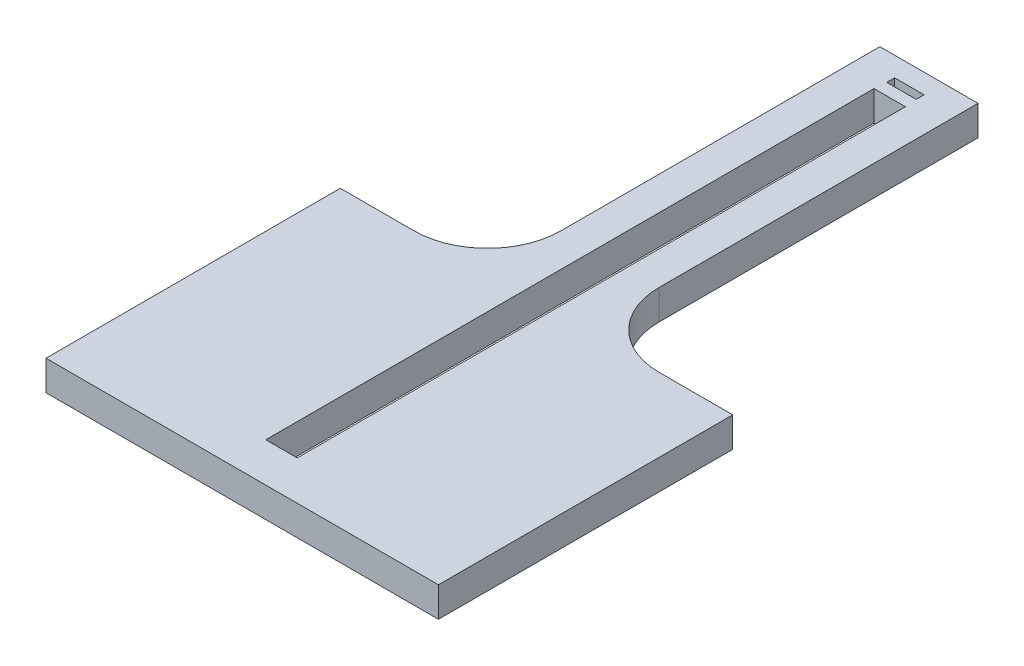
SolidWorks part; units mm, degrees
ref_plane "Front Plane" through (0, 0, 0) normal (0, 0, 1) x (1, 0, 0)
ref_plane "Top Plane" through (0, 0, 0) normal (0, 1, 0) x (1, 0, 0)
ref_plane "Right Plane" through (0, 0, 0) normal (1, 0, 0) x (0, 0, -1)
sketch "Sketch1" plane through (0, 0, 0) normal (0, 1, 0) x (1, 0, 0)
  line L1 (0, 0) -> (40, 0)
  line L2 (0, 0) -> (0, 70)
  line L3 (0, 70) -> (40, 70)
  line L4 (40, 0) -> (40, 70)
  dimension "D1" = 40
  dimension "D2" = 70
extrude "Boss-Extrude1" add sketch "Sketch1" along normal blind 3.05 contours L2 | L1 L4 L3 L2 | L4 region at (20, 0, -35)
sketch "Sketch4" plane through (0, 3.05, 0) normal (0, 1, 0) x (1, 0, 0)
  line L0 (20, 70) -> (20, 68)
  line L1 (0, 70) -> (40, 70) construction
  line L3 (21.5, 68) -> (18.5, 68)
  line L4 (18.5, 68) -> (18.5, 67.2)
  line L5 (18.5, 67.2) -> (21.5, 67.2)
  line L6 (21.5, 67.2) -> (21.5, 68)
  line L7 (20, 67.2) -> (20, 66)
  line L9 (21.6, 66) -> (18.4, 66)
  line L10 (18.4, 66) -> (18.4, 4)
  line L11 (18.4, 4) -> (21.6, 4)
  line L12 (21.6, 4) -> (21.6, 66)
  point P10 (20, 68)
  point P22 (20, 66)
  dimension "D1" = 2
  dimension "D2" = 0.8
  dimension "D3" = 1.2
  dimension "D4" = 3
  dimension "D5" = 62
  dimension "D6" = 3.2
extrude "Cut-Extrude1" cut sketch "Sketch4" against normal blind 10 contours L11 L12 L9 L10 | L5 L6 L3 L4 region at (20, 3.05, -67.6) region at (20, 3.05, -35)
sketch "Sketch5" plane through (0, 3.05, 0) normal (0, 1, 0) x (1, 0, 0)
  line L0 (0, 70) -> (0, 30)
  line L1 (0, 0) -> (0, 70) construction
  line L2 (0, 70) -> (15, 70)
  line L3 (0, 70) -> (40, 70) construction
  line L5 (40, 70) -> (25, 70)
  line L6 (40, 70) -> (40, 30)
  line L7 (40, 0) -> (40, 70) construction
  line L9 (15, 70) -> (15, 30)
  line L10 (15, 30) -> (0, 30)
  line L11 (25, 70) -> (25, 30)
  line L12 (25, 30) -> (40, 30)
  circle A0 centre (7.5, 37.5) radius 7.5
  circle A1 centre (32.5, 37.5) radius 7.5
  line M14 (40, 0) -> (40, 70)
  line M15 (40, 70) -> (0, 70)
  line M16 (0, 70) -> (0, 0)
  dimension "D1" = 40
  dimension "D2" = 15
  dimension "D3" = 40
  dimension "D4" = 15
extrude "Cut-Extrude2" cut sketch "Sketch5" against normal blind 10 contours A0 L9 M15 M16 | A0 | A0 L0 L10 | A1 L6 L11 M15 | A1 | A1 L12 M14 region at (7.5, 3.05, -56.6426) region at (32.5, 3.05, -56.6426) region at (1.6753, 3.05, -31.6753) region at (7.5, 3.05, -37.5) region at (32.5, 3.05, -37.5) region at (38.3247, 3.05, -31.6753)
